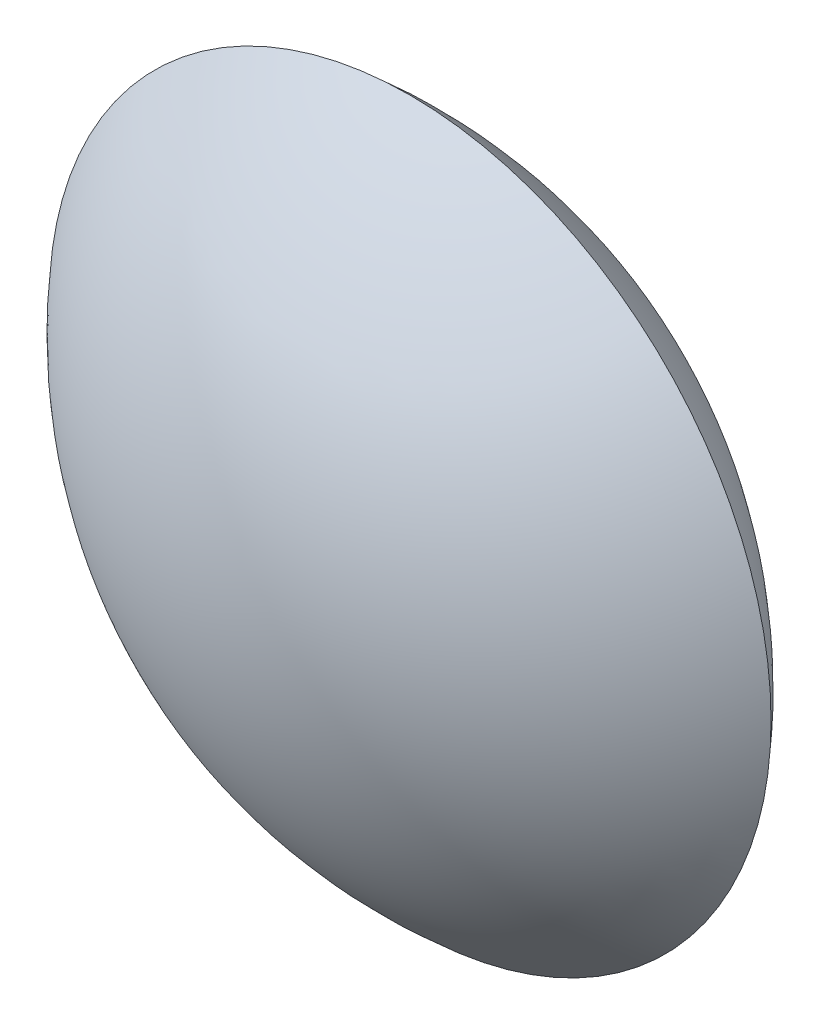
SolidWorks part; units mm, degrees
ref_plane "Front Plane" through (0, 0, 0) normal (0, 0, 1) x (1, 0, 0)
ref_plane "Top Plane" through (0, 0, 0) normal (0, 1, 0) x (1, 0, 0)
ref_plane "Right Plane" through (0, 0, 0) normal (1, 0, 0) x (0, 0, -1)
sketch "Sketch1" plane through (0, 0, 0) normal (0, 1, 0) x (1, 0, 0)
  line L0 (0, 70.3142) -> (0, -70.3142)
  circle A0 centre (0, -130) radius 200.3142
  circle A1 centre (0, 130) radius 200.3142
  point P3 (-152.4, 0)
  point P5 (152.4, 0)
  dimension "D1" = 304.8
  dimension "D2" = 130
  dimension "D3" = 130
ref_axis "Axis1" through (0, 0, -90.8033) along (0, 0, 1)
revolve "Revolve3" add sketch "Sketch1" angle 360 about axis through (0, 0, -90.8033) along (0, 0, 1) region at (-58.7741, 0, 0)
